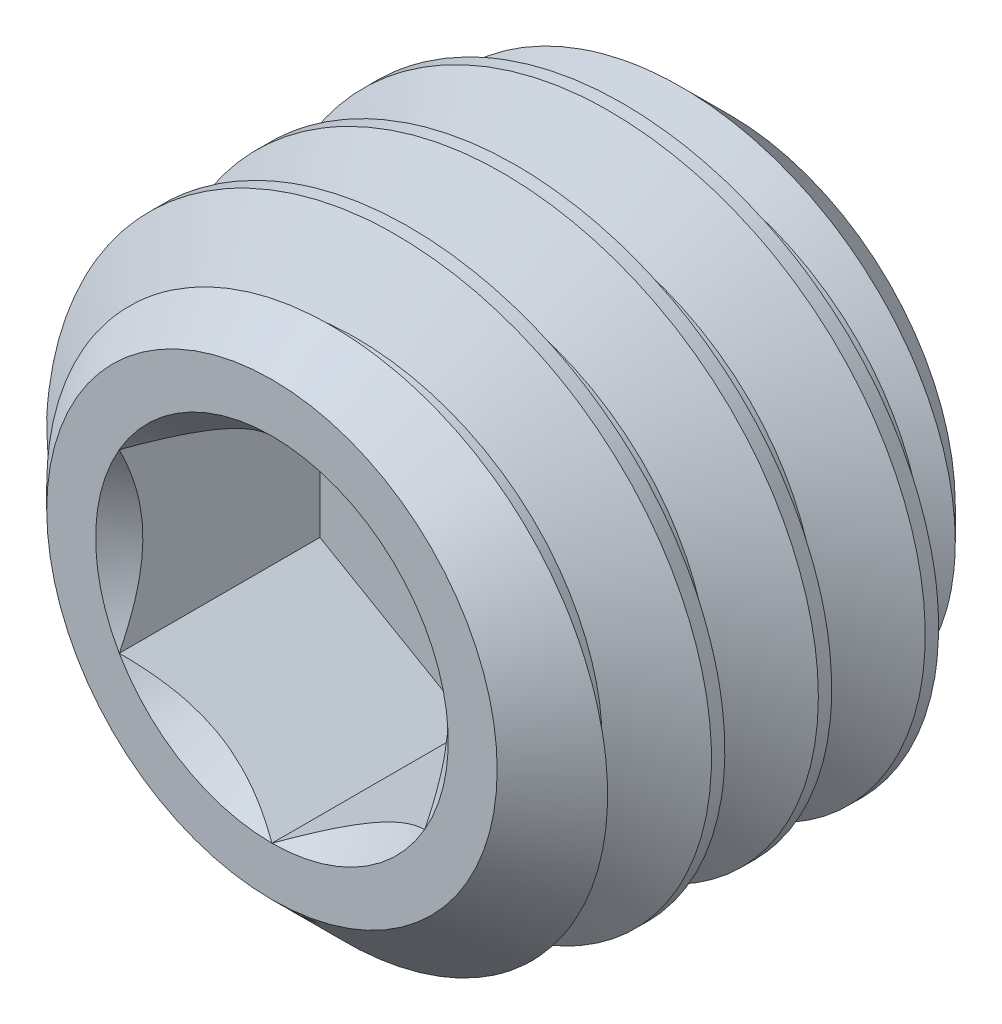
SolidWorks part; units mm, degrees
material "Stainless Steel (ferritic)"
ref_plane "Front Plane" through (0, 0, 0) normal (0, 0, 1) x (1, 0, 0)
ref_plane "Top Plane" through (0, 0, 0) normal (0, 1, 0) x (1, 0, 0)
ref_plane "Right Plane" through (0, 0, 0) normal (1, 0, 0) x (0, 0, -1)
sketch "Sketch1" plane through (0, 0, 0) normal (1, 0, 0) x (0, 0, -1)
  line L0 (-1.5, 0) -> (1.5, 0) construction
  line L1 (-1.5, -2) -> (-1.5, 2) construction
  line L2 (-1.5, -1) -> (-1.5, 1) construction
  line L3 (-1.5, 2) -> (1.5, 2) construction
  line L4 (1.5, 2) -> (1.5, 0) construction
  line L5 (-2.1562, 2.0758) -> (-1.4562, 2.0758)
  line L6 (-1.4562, 2.0758) -> (-1.8062, 1.4696)
  line L7 (-1.8062, 1.4696) -> (-2.1562, 2.0758)
  line L8 (-1.8062, 1.4696) -> (-1.8062, 1.5453)
  line L9 (-1.8062, 2.0758) -> (-1.8062, 2)
  line L10 (-2.1125, 2) -> (-1.5, 2)
  line L11 (-2.1344, 2.0379) -> (-1.4781, 2.0379)
  line L12 (-1.85, 1.5453) -> (-1.7625, 1.5453)
  point P3 (-0.45, -2)
  point P4 (0, 0)
  point P8 (-1.5, 0)
  point P11 (-1.5, 0)
  point P21 (-1.8062, 2)
  point P24 (-1.8063, 2.0379)
  point P27 (-1.8062, 1.5453)
  dimension "Length" = 3
  dimension "Thread Size" = 4
  dimension "Drive Size" = 2
  dimension "Thread Pitch" = 0.7
  dimension "D1" = 0.0875
  dimension "D2" = 1.05
sketch "Sketch2" plane through (0, 0, 0) normal (1, 0, 0) x (0, 0, -1)
  line L1 (-1.5, 0) -> (1.5, 0)
  line L2 (-1.5, 0) -> (-1.5, 2)
  line L3 (-1.5, 2) -> (1.5, 2)
  line L4 (1.5, 0) -> (1.5, 2)
revolve "Revolve1" add sketch "Sketch2" angle 360 about L1
chamfer "Chamfer1" distance 0.525 angle 45 2 edges at (2, 0, -1.5) (2, 0, 1.5)
sketch "Sketch3" plane through (0, 0, 1.5) normal (0, 0, 1) x (1, 0, 0)
  line L0 (0, -1) -> (0, 1) construction
  line L1 (0, 1.1547) -> (-1, 0.5774)
  line L2 (-1, 0.5774) -> (-1, -0.5774)
  line L3 (-1, -0.5774) -> (0, -1.1547)
  line L4 (0, -1.1547) -> (1, -0.5774)
  line L5 (1, -0.5774) -> (1, 0.5774)
  line L6 (1, 0.5774) -> (0, 1.1547)
  line L7 (0, -2) -> (0, 2) construction
  circle A0 centre (0, 0) radius 1 construction
extrude "Cut-Extrude1" cut sketch "Sketch3" against normal blind 1.314
sketch "Sketch4" plane through (0, 0, 1.5) normal (0, 0, 1) x (1, 0, 0)
  line L0 (0, -2) -> (0, 2) construction
  circle A0 centre (0, 0) radius 1.1547
extrude "Cut-Extrude2" cut sketch "Sketch4" against normal blind 1.314 draft 45
sketch "Sketch5" plane through (0, 0, 1.5) normal (0, 0, 1) x (1, 0, 0)
  line L0 (0, -2) -> (0, 2) construction
  circle A0 centre (0, 0) radius 2
curve "Helix/Spiral1" pitch 0.7 height 3.7 radius 2 centre (0, 0, 1.5) axis (0, 0, -1) start towards (0, 1, 0)
sketch "Sketch6" plane through (0, 0, 0) normal (1, 0, 0) x (0, 0, -1)
  line L0 (-2.1344, 2.0379) -> (-1.4781, 2.0379)
  line L1 (-1.4781, 2.0379) -> (-1.7625, 1.5453)
  line L2 (-1.7625, 1.5453) -> (-1.85, 1.5453)
  line L3 (-1.85, 1.5453) -> (-2.1344, 2.0379)
sweep "Cut-Sweep1" cut profiles "Sketch6" path "Helix/Spiral1"
equation "\"D1@Sketch1\"=\"Thread Pitch@Sketch1\"/8"
equation "\"D1@Chamfer1\"=\"Thread Pitch@Sketch1\"*.75"
equation "\"D1@Cut-Extrude1\"=\"Length@Sketch1\"*.438"
equation "\"D1@Cut-Extrude2\"=\"D1@Cut-Extrude1\""
equation "\"D4@Helix/Spiral1\"=\"Thread Pitch@Sketch1\""
equation "\"D3@Helix/Spiral1\"=\"Thread Pitch@Sketch1\"+\"Length@Sketch1\""
equation "\"D2@Sketch1\"=\"Thread Pitch@Sketch1\"*1.5"
